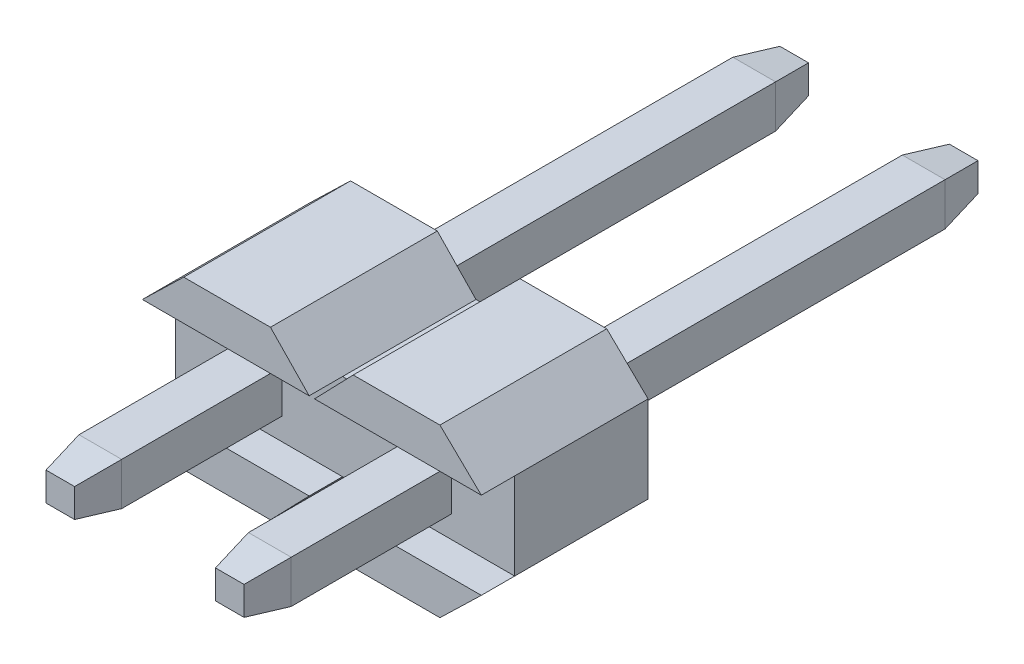
SolidWorks part; units mm, degrees
note: The reader was unsure of these and kept them because the rebuilt part matched: shared geometry of "草图3<2>".
ref_plane "前视基准面" through (0, 0, 0) normal (0, 0, 1) x (1, 0, 0)
ref_plane "上视基准面" through (0, 0, 0) normal (0, 1, 0) x (1, 0, 0)
ref_plane "右视基准面" through (0, 0, 0) normal (1, 0, 0) x (0, 0, -1)
sketch "草图1" plane through (0, 0, 0) normal (0, 0, 1) x (1, 0, 0)
  line L0 (-1.92, 1.25) -> (-2.54, 0.65)
  line L1 (-2.54, 0.65) -> (-2.54, -0.65)
  line L2 (-2.54, -0.65) -> (-1.92, -1.25)
  line L3 (-1.92, -1.25) -> (-0.62, -1.25)
  line L4 (-0.62, -1.25) -> (-0.04, -0.65)
  line L5 (-0.04, -0.65) -> (-0.04, 0.65) construction
  line L6 (-0.04, 0.65) -> (-0.62, 1.25)
  line L7 (-0.62, 1.25) -> (-1.92, 1.25)
  line L8 (-0.04, 0.65) -> (0.04, 0.65)
  line L9 (0, 0.65) -> (0, -0.65) construction
  line L10 (0.04, -0.65) -> (-0.04, -0.65)
  line L11 (-2.54, 0) -> (-0.04, 0) construction
  line L12 (-1.27, -1.25) -> (-1.27, 1.25) construction
  line L13 (0.62, 1.25) -> (1.92, 1.25)
  line L14 (0.04, 0.65) -> (0.62, 1.25)
  line L15 (0.62, -1.25) -> (0.04, -0.65)
  line L16 (1.92, -1.25) -> (0.62, -1.25)
  line L17 (2.54, -0.65) -> (1.92, -1.25)
  line L18 (2.54, 0.65) -> (2.54, -0.65)
  line L19 (1.92, 1.25) -> (2.54, 0.65)
  point P16 (-1.27, 0)
  dimension "D1" = 5.08
  dimension "D2" = 2.5
  dimension "D3" = 2.54
  dimension "D4" = 2.5
  dimension "D5" = 0.6
extrude "凸台-拉伸1" add sketch "草图1" along normal mid plane 2.5
sketch "草图2" plane through (-2.54, 0, 0) normal (-1, 0, 0) x (0, 0, 1)
  line L0 (1.25, -0.65) -> (-1.25, -0.65) construction
  line L1 (1.25, 0.65) -> (0.75, 0.65)
  line L2 (1.25, 0.65) -> (1.25, -0.65)
  line L3 (1.25, -0.65) -> (0.75, -0.65)
  line L4 (0.75, 0.65) -> (0.75, -0.65)
  dimension "D1" = 0.5
extrude "切除-拉伸1" cut sketch "草图2" against normal through all
sketch "草图3" plane through (0, 0, -1.25) normal (0, 0, -1) x (-1, 0, 0)
  line L0 (1.27, 0) -> (-1.27, 0) construction
  line L1 (-0.95, -0.32) -> (-1.59, -0.32)
  line L2 (-0.95, -0.32) -> (-0.95, 0.32)
  line L3 (-0.95, 0.32) -> (-1.59, 0.32)
  line L4 (-1.59, -0.32) -> (-1.59, 0.32)
  line L5 (-0.95, -0.32) -> (-1.59, 0.32) construction
  line L6 (-0.95, 0.32) -> (-1.59, -0.32) construction
  line L8 (0.95, -0.32) -> (1.59, -0.32)
  line L9 (0.95, -0.32) -> (0.95, 0.32)
  line L10 (0.95, 0.32) -> (1.59, 0.32)
  line L11 (1.59, -0.32) -> (1.59, 0.32)
  line L12 (0.95, -0.32) -> (1.59, 0.32) construction
  line L13 (0.95, 0.32) -> (1.59, -0.32) construction
  point P0 (-1.27, 0)
  point P9 (0, 0)
  dimension "D1" = 2.54
  dimension "D2" = 0.64
extrude "凸台-拉伸2" add sketch "草图3" along normal blind 6
extrude "凸台-拉伸3" add sketch "草图3<2>" against normal blind 3 from surface at -2 starting at face at (0, 0, 0.75)
sketch "草图3<2>" plane through (0, 0, -1.25) normal (0, 0, -1) x (-1, 0, 0) same geometry as "草图3"
chamfer "倒角1" distance 0.6 angle 10 16 edges at (1.27, -0.32, 3.75) (0.95, 0, 3.75) (1.27, 0.32, 3.75) (1.59, 0, 3.75) (-1.27, 0.32, 3.75) (-0.95, 0, 3.75) (-1.27, -0.32, 3.75) (-1.59, 0, 3.75) (-1.59, 0, -7.25) (-1.27, -0.32, -7.25) (-0.95, 0, -7.25) (-1.27, 0.32, -7.25) (1.27, -0.32, -7.25) (0.95, 0, -7.25) (1.27, 0.32, -7.25) (1.59, 0, -7.25)
